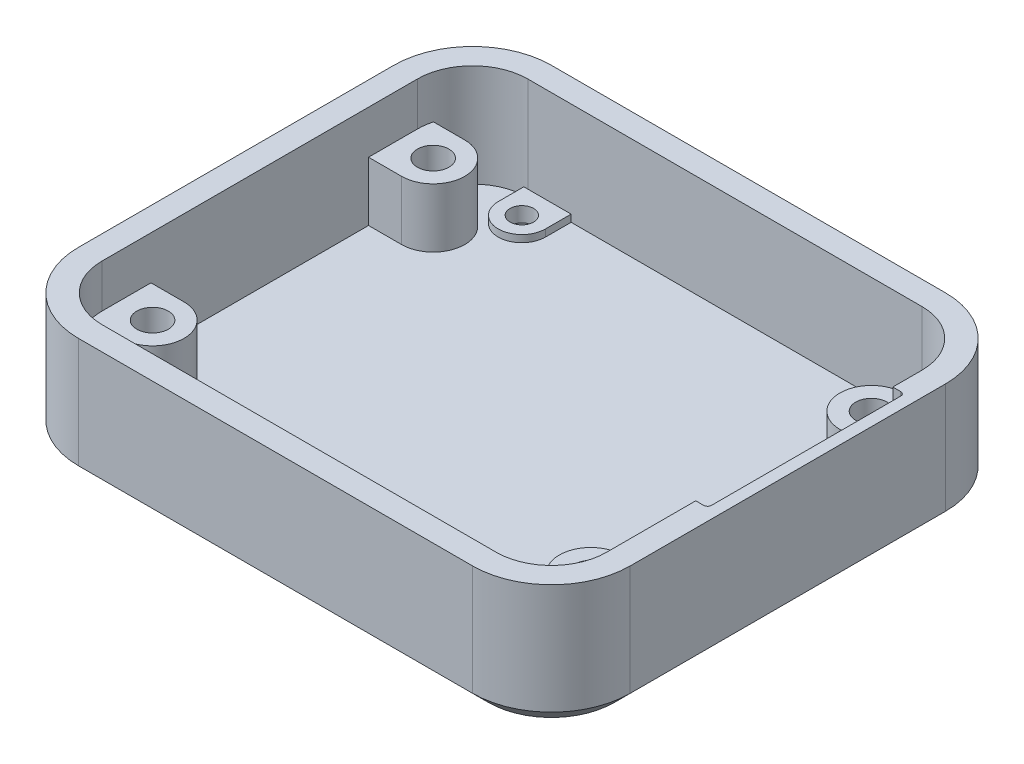
SolidWorks part; units mm, degrees
material "Custom Plastic"
ref_plane "Front Plane" through (0, 0, 0) normal (0, 0, 1) x (1, 0, 0)
ref_plane "Top Plane" through (0, 0, 0) normal (0, 1, 0) x (1, 0, 0)
ref_plane "Right Plane" through (0, 0, 0) normal (1, 0, 0) x (0, 0, -1)
sketch "Sketch1" plane through (0, 0, 0) normal (0, 1, 0) x (1, 0, 0)
  line L1 (-35, -30) -> (35, -30)
  line L2 (-35, -30) -> (-35, 30)
  line L3 (-35, 30) -> (35, 30)
  line L4 (35, -30) -> (35, 30)
  line L5 (-35, -30) -> (35, 30) construction
  line L6 (-35, 30) -> (35, -30) construction
  point P0 (0, 0)
  dimension "D1" = 60
  dimension "D2" = 70
extrude "Boss-Extrude1" add sketch "Sketch1" along normal blind 16
fillet "Fillet1" radius 10 4 edges at (-35, 8, -30) (35, 8, -30) (35, 8, 30) (-35, 8, 30)
shell "Shell1" thickness 3 removed face at (0, 16, 0)
sketch "Sketch2" plane through (0, 3, 0) normal (0, 1, 0) x (1, 0, 0)
  line L0 (0, -1000) -> (0, 49000) construction
  line L1 (-27.8, 17.8) -> (27.8, 17.8) construction
  line L2 (-27.8, 17.8) -> (-27.8, -17.8) construction
  line L3 (-27.8, -17.8) -> (27.8, -17.8) construction
  line L4 (27.8, 17.8) -> (27.8, -17.8) construction
  line L5 (-27.8, 17.8) -> (27.8, -17.8) construction
  line L6 (-27.8, -17.8) -> (27.8, 17.8) construction
  line L7 (-1000, 0) -> (49000, 0) construction
  line L8 (-27.8, 21.8) -> (-31.7646, 21.8)
  line L9 (-27.8, 13.8) -> (-32, 13.8)
  line L10 (-32, 20) -> (-32, -20) construction
  line L12 (32, -20) -> (32, 20) construction
  line L14 (-32, 20) -> (-32, -20) construction
  line L16 (32, -20) -> (32, -13.8)
  line L18 (-32, 20) -> (-32, 13.8)
  line L19 (27.8, 13.8) -> (32, 13.8)
  line L20 (27.8, 21.8) -> (31.7646, 21.8)
  line L21 (27.8, -21.8) -> (31.7646, -21.8)
  line L22 (27.8, -13.8) -> (32, -13.8)
  line L23 (-27.8, -13.8) -> (-32, -13.8)
  line L24 (-27.8, -21.8) -> (-31.7646, -21.8)
  line L25 (32, 13.8) -> (32, 20)
  line L26 (-32, -13.8) -> (-32, -20)
  circle A0 centre (-27.8, 17.8) radius 2
  arc A1 (-27.8, 13.8) -> (-27.8, 21.8) centre (-27.8, 17.8) ccw
  arc A2 (-25, 27) -> (-32, 20) centre (-25, 20) ccw construction
  arc A3 (-32, -20) -> (-25, -27) centre (-25, -20) ccw construction
  arc A4 (25, -27) -> (32, -20) centre (25, -20) ccw construction
  arc A5 (32, 20) -> (25, 27) centre (25, 20) ccw construction
  arc A6 (-32, -20) -> (-31.7646, -21.8) centre (-25, -20) ccw
  arc A7 (31.7646, -21.8) -> (32, -20) centre (25, -20) ccw
  arc A8 (32, 20) -> (31.7646, 21.8) centre (25, 20) ccw
  arc A9 (-31.7646, 21.8) -> (-32, 20) centre (-25, 20) ccw
  arc A10 (27.8, 13.8) -> (27.8, 21.8) centre (27.8, 17.8) cw
  circle A11 centre (27.8, 17.8) radius 2
  circle A12 centre (27.8, -17.8) radius 2
  arc A13 (27.8, -13.8) -> (27.8, -21.8) centre (27.8, -17.8) ccw
  circle A14 centre (-27.8, -17.8) radius 2
  arc A15 (-27.8, -13.8) -> (-27.8, -21.8) centre (-27.8, -17.8) cw
  point P0 (0, 0)
  dimension "D3" = 4
  dimension "D4" = 8
  dimension "D1" = 55.6
  dimension "D2" = 35.6
extrude "Boss-Extrude2" add sketch "Sketch2" along normal blind 7.5
sketch "Sketch4" plane through (0, 16, 0) normal (0, 1, 0) x (1, 0, 0)
  line L0 (32, 16.31) -> (33.5, 16.31)
  line L1 (32, -13.8) -> (32, 13.8) construction
  line L2 (33.5, 16.31) -> (33.5, -8.69)
  line L3 (33.5, -8.69) -> (32, -8.69)
  line L4 (32, -8.69) -> (32, 16.31)
  line L6 (25, 30) -> (-25, 30) construction
  point P4 (32, 3.81)
  point P7 (0, 0)
  dimension "D1" = 1.5
  dimension "D2" = 25
  dimension "D3" = 26.19
extrude "Cut-Extrude1" cut sketch "Sketch4" against normal blind 2
fillet "Fillet2" radius 0.5 4 edges at (33.5, 15, -16.31) (33.5, 15, 8.69) (32.75, 14, 8.69) (32.75, 14, -16.31)
chamfer "Chamfer1" distance 2 angle 45 8 edges at (-32.0711, 0, 27.0711) (0, 0, 30) (32.0711, 0, 27.0711) (35, 0, 0) (32.0711, 0, -27.0711) (0, 0, -30) (-32.0711, 0, -27.0711) (-35, 0, 0)
sketch "Sketch5" plane through (0, 0, 0) normal (0, -1, 0) x (1, 0, 0)
  line L1 (-22.5, -23.75) -> (22.5, -23.75) construction
  line L2 (-22.5, -23.75) -> (-22.5, 23.75) construction
  line L3 (-22.5, 23.75) -> (22.5, 23.75) construction
  line L4 (22.5, -23.75) -> (22.5, 23.75) construction
  line L5 (-22.5, -23.75) -> (22.5, 23.75) construction
  line L6 (-22.5, 23.75) -> (22.5, -23.75) construction
  line L7 (-1000, 0) -> (49000, 0) construction
  line L8 (0, -1000) -> (0, 49000) construction
  circle A0 centre (-22.5, 23.75) radius 1.5
  circle A1 centre (22.5, 23.75) radius 1.5
  circle A2 centre (22.5, -23.75) radius 1.5
  circle A3 centre (-22.5, -23.75) radius 1.5
  point P0 (0, 0)
  dimension "D3" = 3
  dimension "D1" = 45
  dimension "D2" = 47.5
extrude "Cut-Extrude2" cut sketch "Sketch5" against normal up to next
sketch "Sketch6" plane through (0, 0, 0) normal (0, -1, 0) x (1, 0, 0)
  line L0 (-1000, 0) -> (49000, 0) construction
  line L1 (0, -1000) -> (0, 49000) construction
  circle A0 centre (-22.5, 23.75) radius 2.75
  circle A1 centre (-22.5, 23.75) radius 1.5 construction
  circle A2 centre (22.5, 23.75) radius 2.75
  circle A3 centre (22.5, -23.75) radius 2.75
  circle A4 centre (-22.5, -23.75) radius 2.75
  dimension "D1" = 5.5
extrude "Cut-Extrude3" cut sketch "Sketch6" against normal blind 2
sketch "Sketch7" plane through (0, 3, 0) normal (0, 1, 0) x (1, 0, 0)
  line L0 (-1000, 0) -> (49000, 0) construction
  line L1 (0, -1000) -> (0, 49000) construction
  line L3 (-25, -27) -> (25, -27) construction
  line L5 (25, 27) -> (-25, 27) construction
  line L14 (-25, -27) -> (-19.5, -27)
  line L16 (25, 27) -> (19.5, 27)
  line L17 (-19.5, 23.75) -> (-19.5, 27)
  line L18 (-25.5, 23.75) -> (-25.5, 26.9821)
  line L19 (19.5, 23.75) -> (19.5, 27)
  line L20 (25.5, 23.75) -> (25.5, 26.9821)
  line L21 (25.5, -23.75) -> (25.5, -26.9821)
  line L22 (19.5, -23.75) -> (19.5, -27)
  line L23 (-19.5, -23.75) -> (-19.5, -27)
  line L24 (-25.5, -23.75) -> (-25.5, -26.9821)
  line L25 (-19.5, 27) -> (-25, 27)
  line L26 (19.5, -27) -> (25, -27)
  circle A0 centre (-22.5, -23.75) radius 1.5 construction
  circle A1 centre (22.5, -23.75) radius 1.5 construction
  circle A2 centre (22.5, 23.75) radius 1.5 construction
  circle A3 centre (-22.5, 23.75) radius 1.5 construction
  circle A4 centre (-22.5, -23.75) radius 1.5
  circle A5 centre (22.5, -23.75) radius 1.5
  circle A6 centre (22.5, 23.75) radius 1.5
  circle A7 centre (-22.5, 23.75) radius 1.5
  arc A8 (-25.5, 23.75) -> (-19.5, 23.75) centre (-22.5, 23.75) ccw
  arc A9 (32, 20) -> (25, 27) centre (25, 20) ccw construction
  arc A10 (25, -27) -> (32, -20) centre (25, -20) ccw construction
  arc A11 (-32, -20) -> (-25, -27) centre (-25, -20) ccw construction
  arc A12 (-25, 27) -> (-32, 20) centre (-25, 20) ccw construction
  arc A13 (25.5, 26.9821) -> (25, 27) centre (25, 20) ccw
  arc A21 (25, -27) -> (25.5, -26.9821) centre (25, -20) ccw
  arc A22 (-25.5, -26.9821) -> (-25, -27) centre (-25, -20) ccw
  arc A23 (-25, 27) -> (-25.5, 26.9821) centre (-25, 20) ccw
  circle A24 centre (22.5, 23.75) radius 1.5
  arc A25 (25.5, 23.75) -> (19.5, 23.75) centre (22.5, 23.75) cw
  circle A26 centre (22.5, -23.75) radius 1.5
  arc A27 (25.5, -23.75) -> (19.5, -23.75) centre (22.5, -23.75) ccw
  circle A28 centre (-22.5, -23.75) radius 1.5
  arc A29 (-25.5, -23.75) -> (-19.5, -23.75) centre (-22.5, -23.75) cw
  circle M17 centre (-22.5, 23.75) radius 1.5
  circle M18 centre (22.5, 23.75) radius 1.5
  circle M19 centre (22.5, -23.75) radius 1.5
  circle M20 centre (-22.5, -23.75) radius 1.5
  arc M26 (31.7646, 21.8) -> (25, 27) centre (25, 20) ccw
  line M27 (25, 27) -> (-25, 27)
  arc M28 (-25, 27) -> (-31.7646, 21.8) centre (-25, 20) ccw
  arc M36 (-31.7646, -21.8) -> (-25, -27) centre (-25, -20) ccw
  line M37 (-25, -27) -> (25, -27)
  arc M38 (25, -27) -> (31.7646, -21.8) centre (25, -20) ccw
  dimension "D1" = 6
extrude "Boss-Extrude3" add sketch "Sketch7" along normal blind 0.9 contours A29 L24 L23 M36 M37 M20 | L21 A27 L22 M37 M38 M19 | L18 A8 L17 M27 M28 M17 | A25 L20 L19 M26 M27 M18 region at (-25.2471, 3, 26.9089) region at (19.5866, 3, 25.375) region at (25.2471, 3, -26.9089) region at (-19.5866, 3, -25.375)
